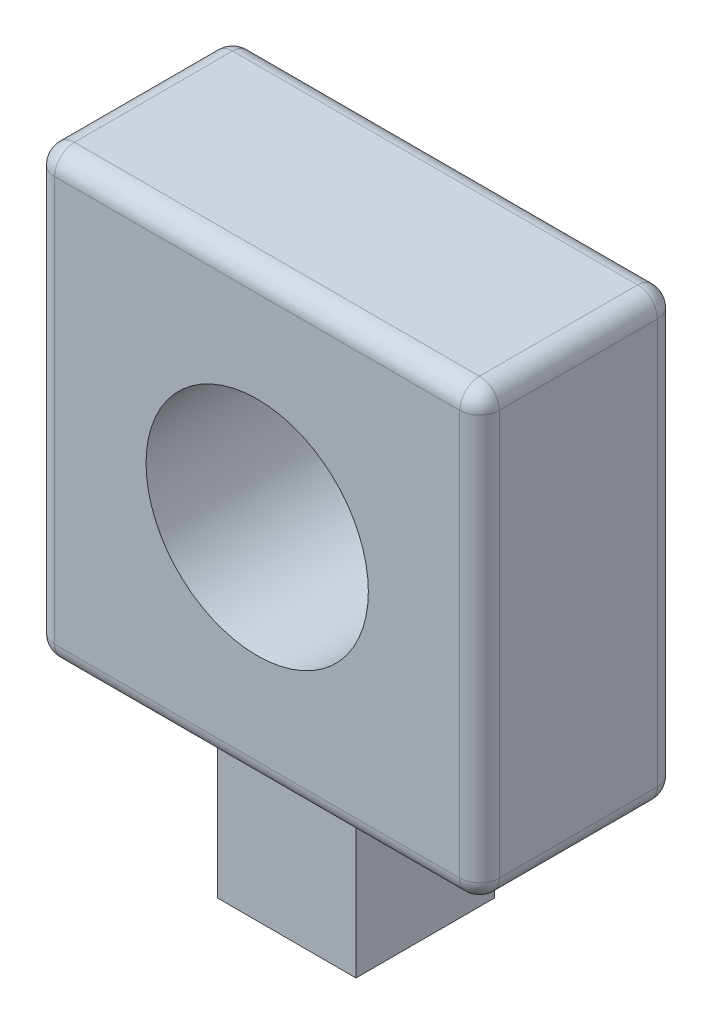
SolidWorks part; units mm, degrees
ref_plane "Front Plane" through (0, 0, 0) normal (0, 0, 1) x (1, 0, 0)
ref_plane "Top Plane" through (0, 0, 0) normal (0, 1, 0) x (1, 0, 0)
ref_plane "Right Plane" through (0, 0, 0) normal (1, 0, 0) x (0, 0, -1)
sketch "Sketch1" plane through (0, 0, 0) normal (0, 1, 0) x (1, 0, 0)
  line L1 (-8.89, -8.89) -> (8.89, -8.89)
  line L2 (-8.89, -8.89) -> (-8.89, 8.89)
  line L3 (-8.89, 8.89) -> (8.89, 8.89)
  line L4 (8.89, -8.89) -> (8.89, 8.89)
  line L5 (-8.89, -8.89) -> (8.89, 8.89) construction
  line L6 (-8.89, 8.89) -> (8.89, -8.89) construction
  point P0 (0, 0)
  dimension "D1" = 17.78
  dimension "D2" = 17.78
extrude "Boss-Extrude1" add sketch "Sketch1" along normal blind 12.7 and the other way blind 6.35
sketch "Sketch2" plane through (0, 12.7, 0) normal (0, 1, 0) x (1, 0, 0)
  line L1 (-28.575, -12.7) -> (28.575, -12.7)
  line L2 (-28.575, -12.7) -> (-28.575, 12.7)
  line L3 (-28.575, 12.7) -> (28.575, 12.7)
  line L4 (28.575, -12.7) -> (28.575, 12.7)
  line L5 (-28.575, -12.7) -> (28.575, 12.7) construction
  line L6 (-28.575, 12.7) -> (28.575, -12.7) construction
  point P0 (0, 0)
  dimension "D1" = 57.15
  dimension "D2" = 25.4
extrude "Boss-Extrude2" add sketch "Sketch2" along normal blind 57.15
sketch "Sketch3" plane through (0, 0, 12.7) normal (0, 0, 1) x (1, 0, 0)
  line L0 (-28.575, 69.85) -> (28.575, 69.85) construction
  line L1 (28.575, 69.85) -> (28.575, 12.7) construction
  circle A0 centre (0, 41.275) radius 14.2875
  dimension "D1" = 28.575
  dimension "D2" = 28.575
  dimension "D3" = 28.575
extrude "Cut-Extrude1" cut sketch "Sketch3" against normal through all
fillet "Fillet1" radius 2.54 12 edges at (28.575, 69.85, 0) (28.575, 12.7, 0) (-28.575, 69.85, 0) (-28.575, 12.7, 0) (28.575, 41.275, -12.7) (0, 69.85, -12.7) (-28.575, 41.275, -12.7) (0, 12.7, -12.7) (-28.575, 41.275, 12.7) (0, 69.85, 12.7) (28.575, 41.275, 12.7) (0, 12.7, 12.7)
